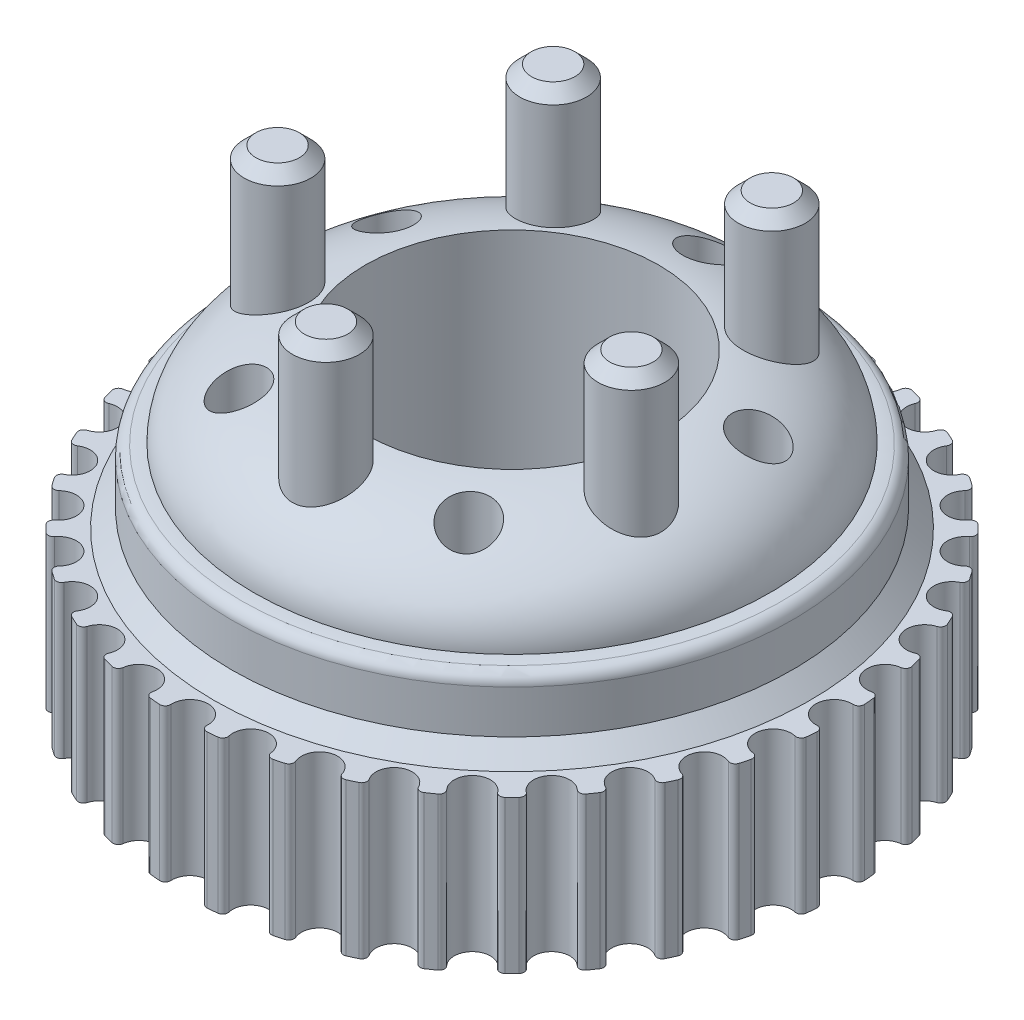
SolidWorks part; units mm, degrees
material "ABS"
ref_plane "Vorne" through (0, 0, 0) normal (0, 0, 1) x (1, 0, 0)
ref_plane "Oben" through (0, 0, 0) normal (0, 1, 0) x (1, 0, 0)
ref_plane "Rechts" through (0, 0, 0) normal (1, 0, 0) x (0, 0, -1)
sketch "Skizze1" plane through (0, 0, 0) normal (0, 1, 0) x (1, 0, 0)
  circle A0 centre (0, 0) radius 28.0764
  dimension "D1" = 56.1528
extrude "Aufsatz-Linear austragen1" add sketch "Skizze1" along normal blind 13
sketch "Zahnung" plane through (0, 13, 0) normal (0, 1, 0) x (1, 0, 0)
  line L0 (0, -34.1344) -> (0, 34.1344) construction
  line L1 (-41.07, 0) -> (41.07, 0) construction
  circle A0 centre (0, 0) radius 28.0764 construction
  circle A1 centre (0, 0) radius 28.6479 construction
  arc A6 (-1.5429, 27.5249) -> (1.5429, 27.5249) centre (0, 27.4382) ccw
  arc A7 (-2.0288, 28.003) -> (-1.5429, 27.5249) centre (-1.996, 27.5504) cw
  arc A8 (2.0288, 28.003) -> (1.5429, 27.5249) centre (1.996, 27.5504) ccw
  arc A9 (-2.0288, 28.003) -> (2.0288, 28.003) centre (0, 0) cw
  point P7 (0, 0)
  point P9 (0, 0)
  point P13 (0, 28.0764)
  dimension "D1" = 56.1528
  dimension "D2" = 57.2958
  dimension "D5" = 0.4538
  dimension "D6" = 1.5453
  dimension "D4" = 0.6382
extrude "Schnitt-Linear austragen1" cut sketch "Zahnung" against normal through all contours A7 A6 A8 A9
pattern_circular "Kreismuster1" count 36 over 360 about axis through (0, 13, 0) along (0, -1, 0) of "Schnitt-Linear austragen1"
sketch "Orangatang Kegel curvature" plane through (0, 0, 0) normal (1, 0, 0) x (0, 0, -1)
  line L0 (-35.3082, 13) -> (35.3082, 13) construction
  line L1 (-11, 26.25) -> (11, 26.25) construction
  line L2 (0, 26.25) -> (0, 13) construction
  line L3 (25.6203, 13) -> (25.2657, 13) construction
  arc B0 (30.8298, 15.1021) -> (34.2569, 13.9913) centre (35.5764, 23.9038) ccw
  arc B1 (-34.2569, 13.9913) -> (-30.8298, 15.1021) centre (-35.5764, 23.9038) ccw
  arc B2 (35.111, 13.1667) -> (34.2569, 13.9913) centre (34.125, 13) ccw
  arc B3 (-34.2569, 13.9913) -> (-35.111, 13.1667) centre (-34.125, 13) ccw
  arc B4 (35.111, 13.1667) -> (35.3082, 13) centre (35.3082, 13.2) ccw
  arc B5 (-35.3082, 13) -> (-35.111, 13.1667) centre (-35.3082, 13.2) ccw
  spline B6 degree 3 poles (11, 26.25) (17.4437, 26.25) (22, 23.3505) (22, 19.25) knots 0 0 0 0 1 1 1 1 weights 1 0.804738 0.804738 1
  spline B7 degree 3 poles (-22, 19.25) (-22, 23.3505) (-17.4437, 26.25) (-11, 26.25) knots 0 0 0 0 1 1 1 1 weights 1 0.804738 0.804738 1
  spline B8 degree 3 poles (22, 19.25) (25.3541, 19.211) (27.7722, 16.8437) (30.6261, 15.212) (30.8298, 15.1021) knots 0 0 0 0 0.687314 0.739788 0.739788 0.739788 0.739788
  spline B9 degree 3 poles (-30.8298, 15.1021) (-30.6261, 15.212) (-27.7722, 16.8437) (-25.3541, 19.211) (-22, 19.25) knots 0 0 0 0 0.052474 0.739788 0.739788 0.739788 0.739788
sketch_block_instance "Orangatang Kegel inner curvature-1"
sketch_block "Orangatang Kegel inner curvature"
sketch "Skizze23" plane through (0, 0, 0) normal (1, 0, 0) x (0, 0, -1)
  line L0 (-25.8928, 13) -> (25.8928, 13) construction
  line L1 (-22, 19.25) -> (-22, 13) construction
  line L2 (0, 13) -> (0, 0) construction
  line L3 (-23.8928, 13) -> (-23.8928, 18.1777)
  line L4 (-12.5, 26.1846) -> (-12.5, 13)
  line L5 (-23.8928, 13) -> (-12.5, 13)
  line L6 (-22.2168, 13) -> (-24.6087, 13) construction
  arc A0 (-34.2569, 13.9913) -> (-30.8298, 15.1021) centre (-35.5764, 23.9038) ccw construction
  arc A1 (-34.2569, 13.9913) -> (-35.111, 13.1667) centre (-34.125, 13) ccw construction
  arc A2 (-35.3082, 13) -> (-35.111, 13.1667) centre (-35.3082, 13.2) ccw construction
  arc A3 (35.111, 13.1667) -> (35.3082, 13) centre (35.3082, 13.2) ccw construction
  arc A4 (35.111, 13.1667) -> (34.2569, 13.9913) centre (34.125, 13) ccw construction
  arc A5 (30.8298, 15.1021) -> (34.2569, 13.9913) centre (35.5764, 23.9038) ccw construction
  arc A6 (-34.2569, 13.9913) -> (-30.8298, 15.1021) centre (-35.5764, 23.9038) ccw construction
  arc A7 (-34.2569, 13.9913) -> (-35.111, 13.1667) centre (-34.125, 13) ccw construction
  arc A8 (-35.3082, 13) -> (-35.111, 13.1667) centre (-35.3082, 13.2) ccw construction
  arc A9 (35.111, 13.1667) -> (35.3082, 13) centre (35.3082, 13.2) ccw construction
  arc A10 (35.111, 13.1667) -> (34.2569, 13.9913) centre (34.125, 13) ccw construction
  arc A11 (30.8298, 15.1021) -> (34.2569, 13.9913) centre (35.5764, 23.9038) ccw construction
  arc A12 (-23.8928, 18.1777) -> (-23.041, 19.1666) centre (-22.8928, 18.1777) cw
  spline S0 degree 3 poles (-22, 19.25) (-22, 23.3505) (-17.4437, 26.25) (-11, 26.25) knots 0 0 0 0 1 1 1 1 weights 1 0.804738 0.804738 1 construction
  spline S1 degree 3 poles (947.7375, 2849.9643) (-99.2351, 32.9341) (5.7912, -34.5311) (-15.5369, 111.2746) (1447.8701, -2595.2435) knots -5.625883 -5.625883 -5.625883 -5.625883 0.052474 6.970934 6.970934 6.970934 6.970934 only from (-30.8298, 15.1021) to (-22, 19.25) construction
  spline S2 degree 3 poles (-971.226, -1716.2713) (13.2287, 92.5147) (2.0434, -22.4982) (87.7045, 25.954) (-601.6564, 1911.7993) knots -5.378569 -5.378569 -5.378569 -5.378569 0.687314 5.649706 5.649706 5.649706 5.649706 only from (22, 19.25) to (30.8298, 15.1021) construction
  spline S3 degree 3 poles (11, 26.25) (17.4437, 26.25) (22, 23.3505) (22, 19.25) knots 0 0 0 0 1 1 1 1 weights 1 0.804738 0.804738 1 construction
  spline S4 degree 3 poles (-22, 19.25) (-22, 22.8812) (-18.2697, 25.6792) (-12.5, 26.1846) knots 0 0 0 0 0.905797 0.905797 0.905797 0.905797 weights 1 0.823132 0.806471 0.950015
  spline S5 degree 3 poles (-23.041, 19.1666) (-22.7055, 19.2169) (-22.3591, 19.2458) (-22, 19.25) knots 0.666203 0.666203 0.666203 0.666203 0.739788 0.739788 0.739788 0.739788
  spline S6 degree 3 poles (22, 19.25) (25.3541, 19.211) (27.7722, 16.8437) (30.6261, 15.212) (30.8298, 15.1021) knots 0 0 0 0 0.687314 0.739788 0.739788 0.739788 0.739788 construction
  spline S7 degree 3 poles (11, 26.25) (17.4437, 26.25) (22, 23.3505) (22, 19.25) knots 0 0 0 0 1 1 1 1 weights 1 0.804738 0.804738 1 construction
  spline S8 degree 3 poles (-30.8298, 15.1021) (-30.6261, 15.212) (-28.3029, 16.5403) (-26.2685, 18.356) (-23.8928, 18.9893) knots 0 0 0 0 0.052474 0.602216 0.602216 0.602216 0.602216 construction
  spline S9 degree 3 poles (-12.5, 26.1846) (-11.9985, 26.2285) (-11.4976, 26.25) (-11, 26.25) knots 0.905797 0.905797 0.905797 0.905797 1 1 1 1 weights 0.950015 0.964944 0.981606 1 construction
  dimension "D3" = 1
  dimension "D2" = 12.5
revolve "Body" add sketch "Skizze23" angle 360 about L2
sketch "Skizze24" plane through (0, 13, 0) normal (0, 1, 0) x (1, 0, 0)
  circle A0 centre (0, 0) radius 12.5 construction
  circle A1 centre (0, 0) radius 12.5
extrude "Hangar hole" cut sketch "Skizze24" against normal through all
sketch "Skizze25" plane through (0, 13, 0) normal (0, 1, 0) x (1, 0, 0)
  circle A0 centre (0, 0) radius 16.655 construction
  circle A1 centre (0, 16.655) radius 2.1
  circle A2 centre (15.8398, 5.1467) radius 2.1
  circle A3 centre (9.7896, -13.4742) radius 2.1
  circle A4 centre (-9.7896, -13.4742) radius 2.1
  circle A5 centre (-15.8398, 5.1467) radius 2.1
  point P15 (0, 0)
  dimension "D1" = 33.31
  dimension "D2" = 4.2
extrude "Mounting holes" cut sketch "Skizze25" against normal through all and the other way through all
ref_plane "Ebene2" through (0, 26.1846, 0) normal (0, -1, 0) x (-1, 0, 0)
ref_axis "Achse2" through (0, 0, 0) along (0, 1, 0)
sketch "Skizze28" plane through (0, 26.1846, 0) normal (0, -1, 0) x (-1, 0, 0)
  line L0 (0, 0) -> (0, 16.655) construction
  line L1 (0, 0) -> (-9.3164, 12.8229) construction
  circle A1 centre (-9.3164, 12.8229) radius 2.85
  circle A2 centre (9.3164, 12.8229) radius 2.85
  circle A3 centre (15.0742, -4.8979) radius 2.85
  circle A4 centre (0, -15.85) radius 2.85
  circle A5 centre (-15.0742, -4.8979) radius 2.85
  circle A6 centre (0, 0) radius 15.85 construction
  point P17 (0, 0)
  dimension "D2" = 5.7
  dimension "D3" = 31.7
  dimension "D1" = 36
extrude "Pins" add sketch "Skizze28" against normal blind 10 and the other way up to surface other way up to face at (0.4863, 24.2463, -18.6979)
chamfer "Fase2" distance 1 angle 45 5 edges at (-15.0742, 36.1846, 2.0479) (0, 36.1846, 13) (15.0742, 36.1846, 2.0479) (9.3164, 36.1846, -15.6729) (-9.3164, 36.1846, -15.6729)
sketch "Skizze29" plane through (0, 0, 0) normal (0, -1, 0) x (1, 0, 0)
  circle A0 centre (-9.7896, 13.4742) radius 3.75
  circle A2 centre (9.7896, 13.4742) radius 3.75
  circle A3 centre (15.8398, -5.1467) radius 3.75
  circle A4 centre (0, -16.655) radius 3.75
  circle A5 centre (-15.8398, -5.1467) radius 3.75
  dimension "D1" = 7.5
extrude "Countersinks" cut sketch "Skizze29" against normal blind 5
sketch "Skizze32" plane through (0, 5, 0) normal (0, -1, 0) x (1, 0, 0)
  line L1 (2.1, -18.755) -> (-2.1, -18.755)
  line L2 (2.1, -18.755) -> (2.1, -14.555)
  line L3 (2.1, -14.555) -> (-2.1, -14.555)
  line L4 (-2.1, -18.755) -> (-2.1, -14.555)
  line L5 (2.1, -18.755) -> (-2.1, -14.555) construction
  line L6 (2.1, -14.555) -> (-2.1, -18.755) construction
  line L7 (4.6462, -18.755) -> (-4.6462, -18.755)
  line L8 (4.6462, -18.755) -> (4.6462, -14.555)
  line L9 (4.6462, -14.555) -> (-4.6462, -14.555)
  line L10 (-4.6462, -18.755) -> (-4.6462, -14.555)
  line L11 (4.6462, -18.755) -> (-4.6462, -14.555) construction
  line L12 (4.6462, -14.555) -> (-4.6462, -18.755) construction
  line L13 (-17.9398, -3.0467) -> (-13.7398, -3.0467)
  line L14 (-17.9398, -3.0467) -> (-17.9398, -7.2467)
  line L15 (-17.9398, -7.2467) -> (-13.7398, -7.2467)
  line L16 (-13.7398, -3.0467) -> (-13.7398, -7.2467)
  line L17 (-17.9398, -3.0467) -> (-13.7398, -7.2467) construction
  line L18 (-17.9398, -7.2467) -> (-13.7398, -3.0467) construction
  line L19 (-11.8896, 11.3742) -> (-7.6896, 11.3742)
  line L20 (-11.8896, 11.3742) -> (-11.8896, 15.5742)
  line L21 (-11.8896, 15.5742) -> (-7.6896, 15.5742)
  line L22 (-7.6896, 11.3742) -> (-7.6896, 15.5742)
  line L23 (-11.8896, 11.3742) -> (-7.6896, 15.5742) construction
  line L24 (-11.8896, 15.5742) -> (-7.6896, 11.3742) construction
  line L25 (7.6896, 15.5742) -> (11.8896, 15.5742)
  line L26 (7.6896, 15.5742) -> (7.6896, 11.3742)
  line L27 (7.6896, 11.3742) -> (11.8896, 11.3742)
  line L28 (11.8896, 15.5742) -> (11.8896, 11.3742)
  line L29 (7.6896, 15.5742) -> (11.8896, 11.3742) construction
  line L30 (7.6896, 11.3742) -> (11.8896, 15.5742) construction
  line L31 (13.7398, -3.0467) -> (17.9398, -3.0467)
  line L32 (13.7398, -3.0467) -> (13.7398, -7.2467)
  line L33 (13.7398, -7.2467) -> (17.9398, -7.2467)
  line L34 (17.9398, -3.0467) -> (17.9398, -7.2467)
  line L35 (13.7398, -3.0467) -> (17.9398, -7.2467) construction
  line L36 (13.7398, -7.2467) -> (17.9398, -3.0467) construction
  line L37 (-13.7398, -9.3342) -> (-17.9398, -9.3342)
  line L38 (-13.7398, -9.3342) -> (-13.7398, -0.9592)
  line L39 (-13.7398, -0.9592) -> (-17.9398, -0.9592)
  line L40 (-17.9398, -9.3342) -> (-17.9398, -0.9592)
  line L41 (-13.7398, -9.3342) -> (-17.9398, -0.9592) construction
  line L42 (-13.7398, -0.9592) -> (-17.9398, -9.3342) construction
  line L43 (-5.8393, 11.3742) -> (-13.7398, 11.3742)
  line L44 (-5.8393, 11.3742) -> (-5.8393, 15.5742)
  line L45 (-5.8393, 15.5742) -> (-13.7398, 15.5742)
  line L46 (-13.7398, 11.3742) -> (-13.7398, 15.5742)
  line L47 (-5.8393, 11.3742) -> (-13.7398, 15.5742) construction
  line L48 (-5.8393, 15.5742) -> (-13.7398, 11.3742) construction
  line L49 (14.2259, 11.3742) -> (5.3532, 11.3742)
  line L50 (14.2259, 11.3742) -> (14.2259, 15.5742)
  line L51 (14.2259, 15.5742) -> (5.3532, 15.5742)
  line L52 (5.3532, 11.3742) -> (5.3532, 15.5742)
  line L53 (14.2259, 11.3742) -> (5.3532, 15.5742) construction
  line L54 (14.2259, 15.5742) -> (5.3532, 11.3742) construction
  line L55 (17.9398, -0.1063) -> (13.7398, -0.1063)
  line L56 (17.9398, -0.1063) -> (17.9398, -10.1871)
  line L57 (17.9398, -10.1871) -> (13.7398, -10.1871)
  line L58 (13.7398, -0.1063) -> (13.7398, -10.1871)
  line L59 (17.9398, -0.1063) -> (13.7398, -10.1871) construction
  line L60 (17.9398, -10.1871) -> (13.7398, -0.1063) construction
  circle A0 centre (0, -16.655) radius 3.75 construction
  circle A1 centre (0, -16.655) radius 2.1 construction
  circle A2 centre (0, -16.655) radius 3.75
  circle A3 centre (0, -16.655) radius 2.1
  circle A4 centre (15.8398, -5.1467) radius 2.1 construction
  circle A5 centre (9.7896, 13.4742) radius 2.1 construction
  circle A6 centre (-9.7896, 13.4742) radius 2.1 construction
  circle A7 centre (-15.8398, -5.1467) radius 2.1 construction
  circle A8 centre (15.8398, -5.1467) radius 2.1
  circle A9 centre (9.7896, 13.4742) radius 2.1
  circle A10 centre (-9.7896, 13.4742) radius 2.1
  circle A11 centre (-15.8398, -5.1467) radius 2.1
  circle A12 centre (15.8398, -5.1467) radius 3.75 construction
  circle A13 centre (9.7896, 13.4742) radius 3.75 construction
  circle A14 centre (-15.8398, -5.1467) radius 3.75 construction
  circle A15 centre (-9.7896, 13.4742) radius 3.75 construction
  circle A16 centre (15.8398, -5.1467) radius 3.75
  circle A17 centre (9.7896, 13.4742) radius 3.75
  circle A18 centre (-15.8398, -5.1467) radius 3.75
  circle A19 centre (-9.7896, 13.4742) radius 3.75
  circle M6 centre (0, -16.655) radius 3.75
extrude "Aufsatz-Linear austragen6" add sketch "Skizze32" along normal blind 0.4 contours L9 L3 M6 | L7 L1 M6 | L40 A18 L14 | L38 A18 L16 | L45 A19 L21 | L43 A19 L19 | L51 A17 L25 | L49 A17 L27 | L56 A16 L34 | L58 A16 L32 region at (0, 5, -19.4293) region at (0, 5, -13.8807) region at (-18.6141, 5, -5.1467) region at (-13.0656, 5, -5.1467) region at (-9.7896, 5, 10.6999) region at (-9.7896, 5, 16.2485) region at (9.7896, 5, 16.2485) region at (9.7896, 5, 10.6999) region at (13.0656, 5, -5.1467) region at (18.6141, 5, -5.1467)
extrude "Aufsatz-Linear austragen7" add sketch "Skizze32<3>" along normal blind 0.2 contours L4 L9 L7 M6 | L9 L2 L7 M6 | L45 A19 L43 L20 | L43 A19 L45 L22 | L51 A17 L49 L26 | L49 A17 L51 L28 | L56 A16 L58 L31 | L58 A16 L56 L33 | L38 A18 L40 L13 | L40 A18 L38 L15 region at (2.8341, 5, -16.655) region at (-2.8341, 5, -16.655) region at (-15.8398, 5, -2.3125) region at (-15.8398, 5, -7.9808) region at (-12.6237, 5, 13.4742) region at (-6.9554, 5, 13.4742) region at (6.9554, 5, 13.4742) region at (12.6237, 5, 13.4742) region at (15.8398, 5, -2.3125) region at (15.8398, 5, -7.9808)
sketch "Skizze32<3>" plane through (0, 5, 0) normal (0, -1, 0) x (1, 0, 0) same geometry as "Skizze32"
chamfer "Fase3" distance 1.5 angle 45 1 edges at (0, 13, 23.8928)
sketch "Skizze33" plane through (0, 0, 0) normal (0, -1, 0) x (1, 0, 0)
  line L0 (0, -16.655) -> (0, 0) construction
  line L5 (0, -12.3647) -> (-1.0095, -13.0434)
  line L6 (-1.0095, -13.0434) -> (1.0095, -13.0434)
  line L7 (1.0095, -13.0434) -> (0, -12.3647)
  arc A5 (3.1068, -14.555) -> (-3.1068, -14.555) centre (0, -16.655) ccw construction
  circle A6 centre (0, -16.655) radius 3.75 construction
extrude "Schnitt-Linear austragen7" cut sketch "Skizze33" against normal up to surface (4.6 mm away) up to face at (0, 4.6, -13.73)
fillet "Verrundung2" [suppressed] radius 0.6
pattern_circular "Kreismuster3" count 5 over 360 about axis through (0, 0, 0) along (0, 1, 0) of "Schnitt-Linear austragen7", "Verrundung2"
sketch "Skizze7" plane through (0, 0, 0) normal (1, 0, 0) x (0, 0, -1)
  line L0 (0, 13) -> (13.25, 13)
  line L1 (13.25, 13) -> (13.25, 24)
  line L2 (0, 37.35) -> (5.3073, 35.3934)
  line L3 (0, 13) -> (0, 37.35)
  line L4 (25.3928, 13) -> (-25.3928, 13) construction
  arc A0 (5.3073, 35.3934) -> (13.25, 24) centre (1.107, 24) cw
  dimension "D2" = 12.143
  dimension "D1" = 13.25
  dimension "D3" = 11
  dimension "D4" = 24.35
sketch "Skizze12" plane through (0, 13, 0) normal (0, 1, 0) x (1, 0, 0)
  circle A0 centre (0, 0) radius 4
  dimension "D1" = 8
equation "\"OD\"= \"PD\" - ( 2 * \"U\" )"
equation "\"D1@Zahnung\" = \"OD\""
equation "\"PD\"= \"NT\" * \"Pitch\" / PI"
equation "\"D2@Zahnung\" = \"PD\""
equation "\"Width\"= 13mm"
equation "\"D1@Aufsatz-Linear austragen1\"=\"Width\""
equation "\"Pitch\"= 5mm"
equation "\"NT\"= 36"
equation "\"U\"= 0.0225in"
equation "\"TPD1\"= 2.18354mm"
equation "\"TPR1\"= 1.54533mm"
equation "\"TPR2\"= 0.4538mm"
equation "\"AS\"= 360grad / \"NT\""
equation "\"D1@Skizze1\"=\"OD\""
equation "\"D4@Zahnung\" = \"TPD1\" - \"TPR1\""
equation "\"D5@Zahnung\" = \"TPR2\""
equation "\"D6@Zahnung\" = \"TPR1\""
equation "\"D1@Kreismuster1\"=\"NT\""
